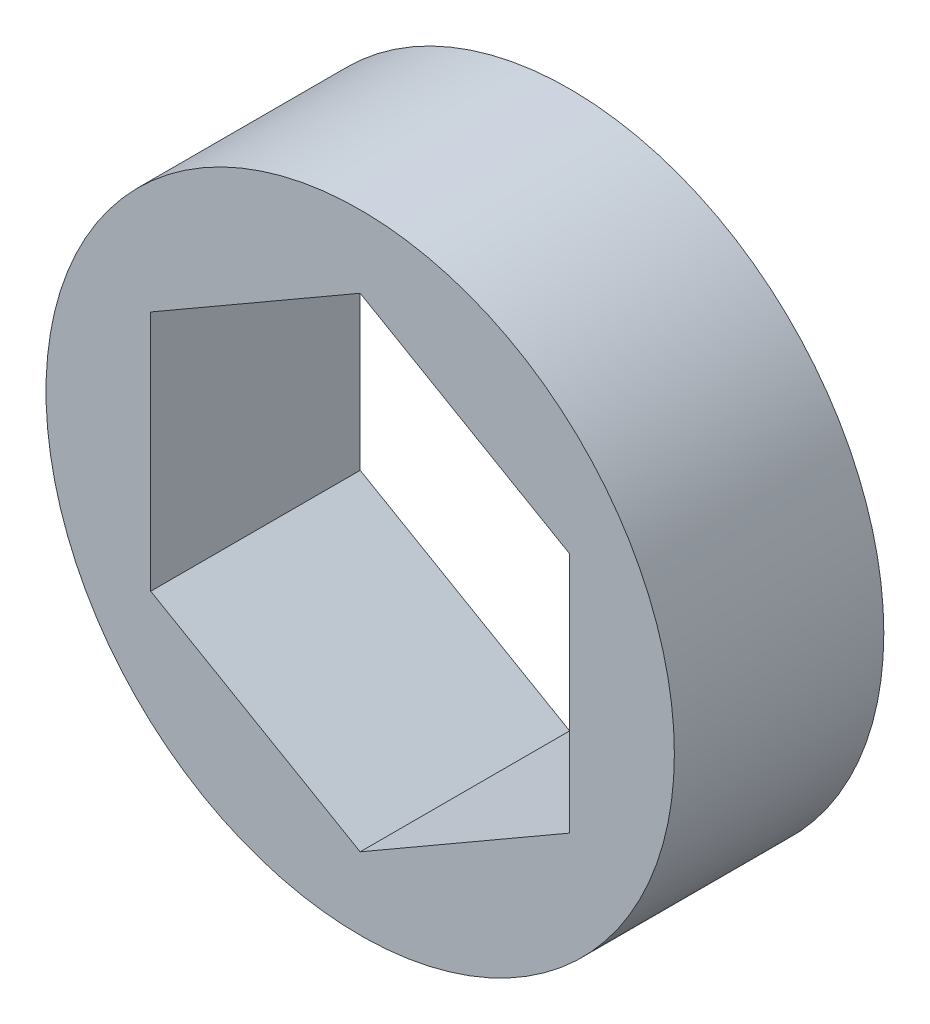
SolidWorks part; units mm, degrees
material "Nylon 101"
ref_plane "Front Plane" through (0, 0, 0) normal (0, 0, 1) x (1, 0, 0)
ref_plane "Top Plane" through (0, 0, 0) normal (0, 1, 0) x (1, 0, 0)
ref_plane "Right Plane" through (0, 0, 0) normal (1, 0, 0) x (0, 0, -1)
sketch "Sketch2" plane through (0, 0, 0) normal (0, 0, 1) x (1, 0, 0)
  line L1 (0, 7.3323) -> (-6.35, 3.6662)
  line L2 (-6.35, 3.6662) -> (-6.35, -3.6662)
  line L3 (-6.35, -3.6662) -> (0, -7.3323)
  line L4 (0, -7.3323) -> (6.35, -3.6662)
  line L5 (6.35, -3.6662) -> (6.35, 3.6662)
  line L6 (6.35, 3.6662) -> (0, 7.3323)
  circle A0 centre (0, 0) radius 6.35 construction
  circle A1 centre (0, 0) radius 9.525
  dimension "D1" = 19.05
  dimension ".5" = 12.7
extrude "Boss-Extrude1" add sketch "Sketch2" along normal blind 6.35
